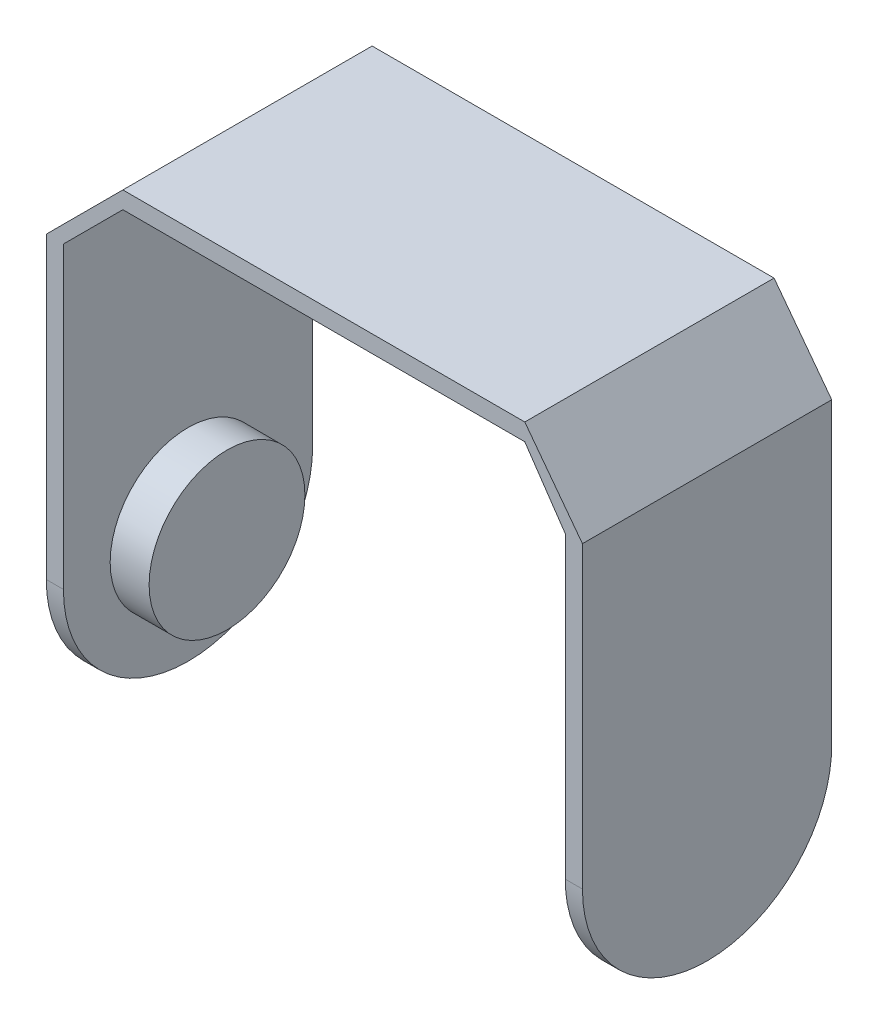
SolidWorks part; units mm, degrees
ref_plane "Front Plane" through (0, 0, 0) normal (0, 0, 1) x (1, 0, 0)
ref_plane "Top Plane" through (0, 0, 0) normal (0, 1, 0) x (1, 0, 0)
ref_plane "Right Plane" through (0, 0, 0) normal (1, 0, 0) x (0, 0, -1)
sketch "Sketch1" plane through (0, 0, 0) normal (0, 0, 1) x (1, 0, 0)
  line L0 (0, 0) -> (0, 54.4)
  line L2 (-5.2012, 64.2289) -> (-56.8012, 64.2289)
  line L3 (-56.8012, 64.2289) -> (-66.6301, 54.4)
  line L4 (-66.6301, 54.4) -> (-66.6301, 0)
  line L5 (-66.6301, 0) -> (-64.4301, 0)
  line L6 (-64.4301, 0) -> (-64.4301, 54.4)
  line L7 (-64.4301, 54.4) -> (-56.8012, 62.0289)
  line L8 (-56.8012, 62.0289) -> (-5.2012, 62.0289)
  line L10 (2.2, 54.4) -> (2.2, 0.0003)
  line L11 (0, 0) -> (2.2, 0.0003)
  line L12 (-5.2012, 62.0289) -> (0, 54.4)
  line L13 (-5.2012, 64.2289) -> (2.2, 54.4)
  dimension "D1" = 2.2
  dimension "D2" = 2.2
  dimension "D3" = 2.2
extrude "Boss-Extrude1" add sketch "Sketch1" along normal blind 32 contours L4 L5 L6 L7 L8 L12 L0 L11 L10 L13 L2 L3
fillet "Fillet1" radius 16 2 edges at (-65.5301, 0, 0) (-65.5301, 0, 32)
fillet "Fillet2" radius 16 2 edges at (1.1, 0.0001, 32) (1.1, 0.0001, 0)
sketch "Sketch2" plane through (-64.4301, 0, 0) normal (1, 0, 0) x (0, 0, -1)
  circle A0 centre (-16, 16) radius 16
  circle A1 centre (-16, 16) radius 10
extrude "Boss-Extrude2" add sketch "Sketch2" along normal blind 5 contours A1
ref_plane "Plane1" through (-32.215, 0, 0) normal (1, 0, 0) x (0, 0, -1)
mirror "Mirror1" about plane through (-32.215, 0, 0) normal (1, 0, 0) of "Boss-Extrude2"
